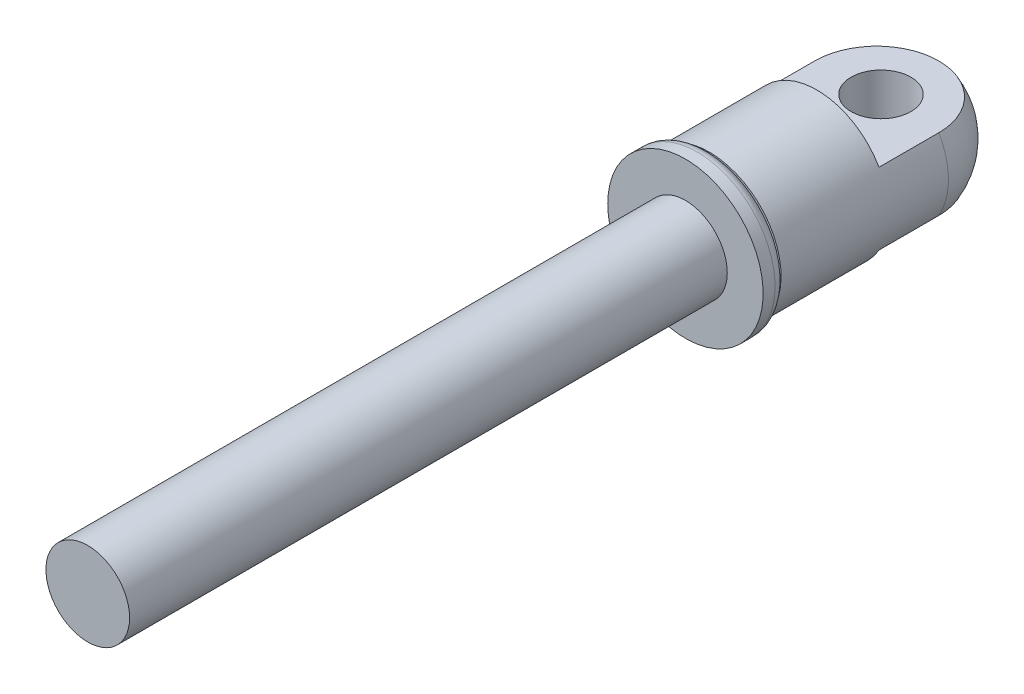
SolidWorks part; units mm, degrees
ref_plane "Plan de face" through (0, 0, 0) normal (0, 0, 1) x (1, 0, 0)
ref_plane "Plan de dessus" through (0, 0, 0) normal (0, 1, 0) x (1, 0, 0)
ref_plane "Plan de droite" through (0, 0, 0) normal (1, 0, 0) x (0, 0, -1)
sketch "Esquisse1" plane through (0, 0, 0) normal (0, 0, 1) x (1, 0, 0)
  circle A0 centre (0, 0) radius 3.5
  dimension "D1" = 7
extrude "Boss.-Extru.1" add sketch "Esquisse1" along normal blind 50
sketch "Esquisse2" plane through (0, 0, 0) normal (0, 0, -1) x (-1, 0, 0)
  circle A0 centre (0, 0) radius 6.5
  dimension "D1" = 13
extrude "Boss.-Extru.2" add sketch "Esquisse2" along normal blind 2
fillet "Congé1" radius 1 1 edges at (-6.5, 0, -2)
sketch "Esquisse3" plane through (0, 0, -2) normal (0, 0, -1) x (-1, 0, 0)
  circle A0 centre (0, 0) radius 6
  dimension "D1" = 12
extrude "Boss.-Extru.3" add sketch "Esquisse3" along normal blind 20
sketch "Esquisse4" plane through (0, 0, -22) normal (0, 0, -1) x (-1, 0, 0)
  line L0 (-5.1962, -3) -> (5.1962, -3)
  line L1 (0, 0) -> (-6, 0) construction
  line L2 (-5.1962, 3) -> (5.1962, 3)
  circle A0 centre (0, 0) radius 6
  circle M4 centre (0, 0) radius 6
  dimension "D2" = 12
  dimension "D1" = 3
extrude "Enlèv. mat.-Extru.1" cut sketch "Esquisse4" against normal blind 11 contours L0 M4 | L2 M4
fillet "Congé3" radius 6 2 edges at (6, 0, -22) (-6, 0, -22)
sketch "Esquisse5" plane through (0, 3, 0) normal (0, 1, 0) x (1, 0, 0)
  circle A0 centre (0, 16.359) radius 2.5
  dimension "D1" = 5
extrude "Enlèv. mat.-Extru.2" cut sketch "Esquisse5" against normal up to surface (6 mm away) up to face at (0, -3, -14.799)
